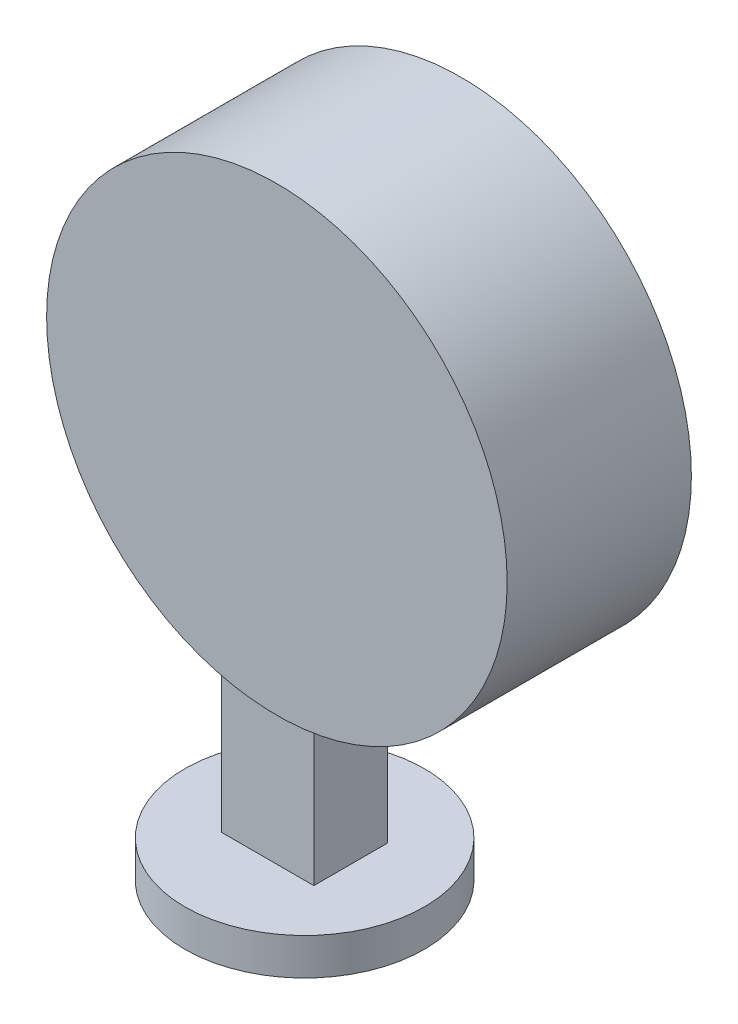
SolidWorks part; units mm, degrees
ref_plane "Front Plane" through (0, 0, 0) normal (0, 0, 1) x (1, 0, 0)
ref_plane "Top Plane" through (0, 0, 0) normal (0, 1, 0) x (1, 0, 0)
ref_plane "Right Plane" through (0, 0, 0) normal (1, 0, 0) x (0, 0, -1)
sketch "Sketch1" plane through (0, 0, 0) normal (0, 1, 0) x (1, 0, 0)
  circle A0 centre (0, 0) radius 6.5
  dimension "D1" = 13
extrude "Boss-Extrude1" add sketch "Sketch1" along normal blind 2
sketch "Sketch2" plane through (0, 0, 0) normal (0, 0, 1) x (1, 0, 0)
  line L0 (6.5, 2) -> (-6.5, 2) construction
  line L1 (6.5, 2) -> (-6.5, 2) construction
  line L2 (-2.5, 2) -> (-2.5, 21.0058)
  line L3 (2.5, 2) -> (2.5, 21.0058)
  line L4 (-2.5, 2) -> (2.5, 2)
  arc A0 (-2.5, 21.0058) -> (3.4942, 27) centre (3.4942, 21.0058) cw
  arc A1 (2.5, 21.0058) -> (3.4942, 22) centre (3.4942, 21.0058) cw
  arc A2 (3.4942, 22) -> (3.4942, 27) centre (3.4942, 24.5) ccw
  point P10 (0, 2)
  dimension "D1" = 5
  dimension "D2" = 90
  dimension "D3" = 90
  dimension "D4" = 5
  dimension "D5" = 25
extrude "Boss-Extrude2" add sketch "Sketch2" along normal blind 2 and the other way blind 2
sketch "Sketch3" plane through (0, 0, 0) normal (0, 0, 1) x (1, 0, 0)
  arc A0 (3.4942, 22) -> (3.4942, 27) centre (3.4942, 24.5) ccw construction
  arc A1 (3.4942, 22) -> (3.4942, 27) centre (3.4942, 24.5) ccw construction
  circle A2 centre (3.4942, 24.5) radius 12.5
  dimension "D1" = 25
extrude "Boss-Extrude3" add sketch "Sketch3" along normal blind 5 and the other way blind 5
